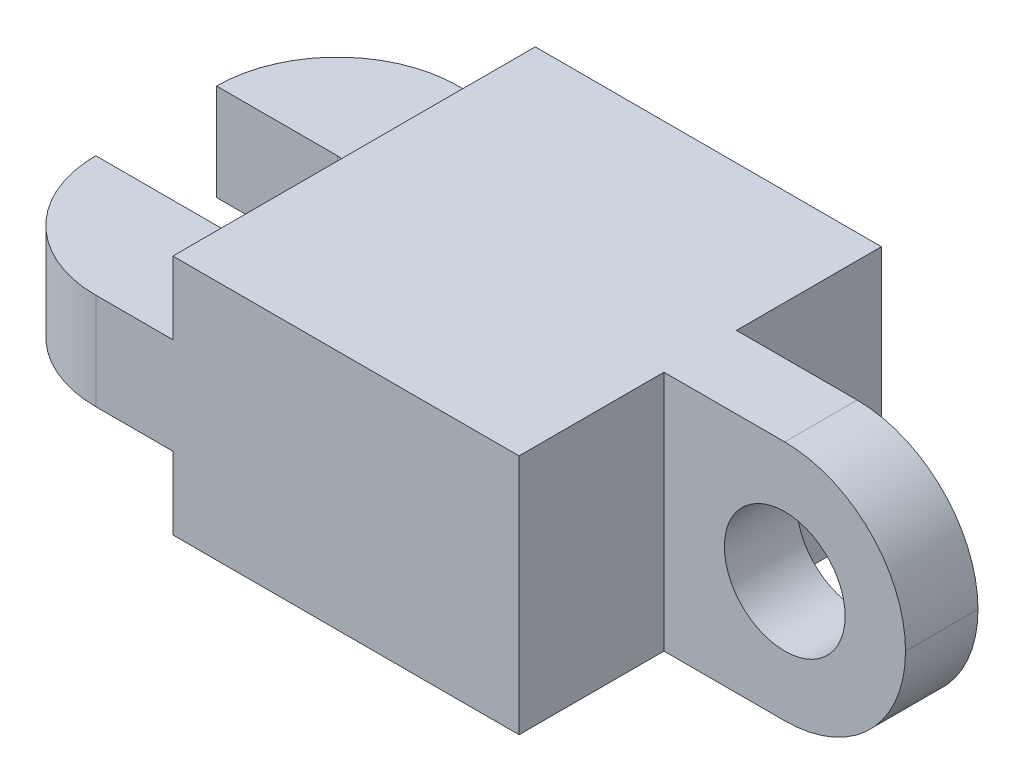
SolidWorks part; units mm, degrees
ref_plane "Front Plane" through (0, 0, 0) normal (0, 0, 1) x (1, 0, 0)
ref_plane "Top Plane" through (0, 0, 0) normal (0, 1, 0) x (1, 0, 0)
ref_plane "Right Plane" through (0, 0, 0) normal (1, 0, 0) x (0, 0, -1)
sketch "Sketch1" plane through (0, 0, 0) normal (0, 1, 0) x (1, 0, 0)
  line L0 (-50, -25) -> (0, -25)
  line L5 (0, 25) -> (-50, 25)
  line L6 (0, 75) -> (175.22, 75)
  line L7 (175.22, 75) -> (175.22, 15)
  line L8 (175.22, 15) -> (275.22, 15)
  line L9 (275.22, 15) -> (275.22, -15)
  line L10 (275.22, -15) -> (175.22, -15)
  line L11 (175.22, -15) -> (175.22, -75)
  line L12 (175.22, -75) -> (0, -75)
  line L13 (0, 0) -> (393.1429, 0) construction
  line L14 (0, 0) -> (0, 205.1429) construction
  arc A0 (0, -25) -> (0, 25) centre (0, 0) ccw
  arc A1 (-50, 25) -> (0, 75) centre (0, 25) cw
  arc A2 (0, -75) -> (-50, -25) centre (0, -25) cw
  point P5 (0, 0)
  point P19 (-74.8571, 75)
  point P21 (0, 0)
  point P22 (0, 0)
  point P23 (-228.1442, 168.0831)
  dimension "D1" = 50
  dimension "D2" = 25
  dimension "D3" = 30
  dimension "D4" = 175.22
  dimension "D5" = 100
extrude "Boss-Extrude1" add sketch "Sketch1" along normal blind 50 and the other way blind 50
fillet "Fillet1" radius 50 2 edges at (275.22, 50, 0) (275.22, -50, 0)
sketch "Sketch4" plane through (0, 0, 25) normal (0, 0, -1) x (-1, 0, 0)
  line L0 (0, -50) -> (0, 50) construction
  line L1 (0, 20) -> (50, 20)
  line L3 (0, -20) -> (50, -20)
  line L5 (0, 0) -> (158.5893, 0) construction
  line L7 (50, 20) -> (50, 50)
  line L8 (0, 20) -> (-31.92, 20)
  line L9 (-175.22, -50) -> (0, -50) construction
  line L10 (50, -50) -> (50, 50)
  line L11 (50, 50) -> (0, 50)
  line L12 (0, 50) -> (0, -50)
  line L13 (0, -50) -> (50, -50)
  line L14 (50, -50) -> (50, -20)
  line L15 (50, 50) -> (0, 50)
  line L17 (0, -50) -> (50, -50)
  line L18 (-175.22, 50) -> (0, 50) construction
  line L19 (0, -20) -> (-31.92, -20)
  line L20 (-31.92, -50) -> (0, -50)
  line L21 (-31.92, 50) -> (0, 50)
  line L22 (-225.22, 0) -> (-125.22, 0) construction
  line L23 (-31.92, 50) -> (-31.92, 20)
  line L24 (-31.92, -20) -> (-31.92, -50)
  dimension "D2" = 40
  dimension "D3" = 100
  dimension "D4" = 93.3
  dimension "D1" = 0
extrude "Cut-Extrude1" cut sketch "Sketch4" along normal through all and the other way through all
hole_wizard "Hole1" positions "Sketch5" profile "Sketch6" legacy end condition through all
sketch "Sketch5" plane through (0, 0, -15) normal (0, 0, -1) x (-1, 0, 0)
  point P0 (-225.22, 0)
sketch "Sketch6" plane through (225.22, 0, -15) normal (1, 0, 0) x (0, 1, 0)
  line L0 (0, 0) -> (0, 90)
  line L1 (0, 90) -> (25, 90)
  line L2 (25, 90) -> (25, 0)
  line L3 (25, 0) -> (0, 0)
  line L4 (0, 110) -> (0, -10) construction
  dimension "Diameter" = 50
  dimension "Depth" = 90
